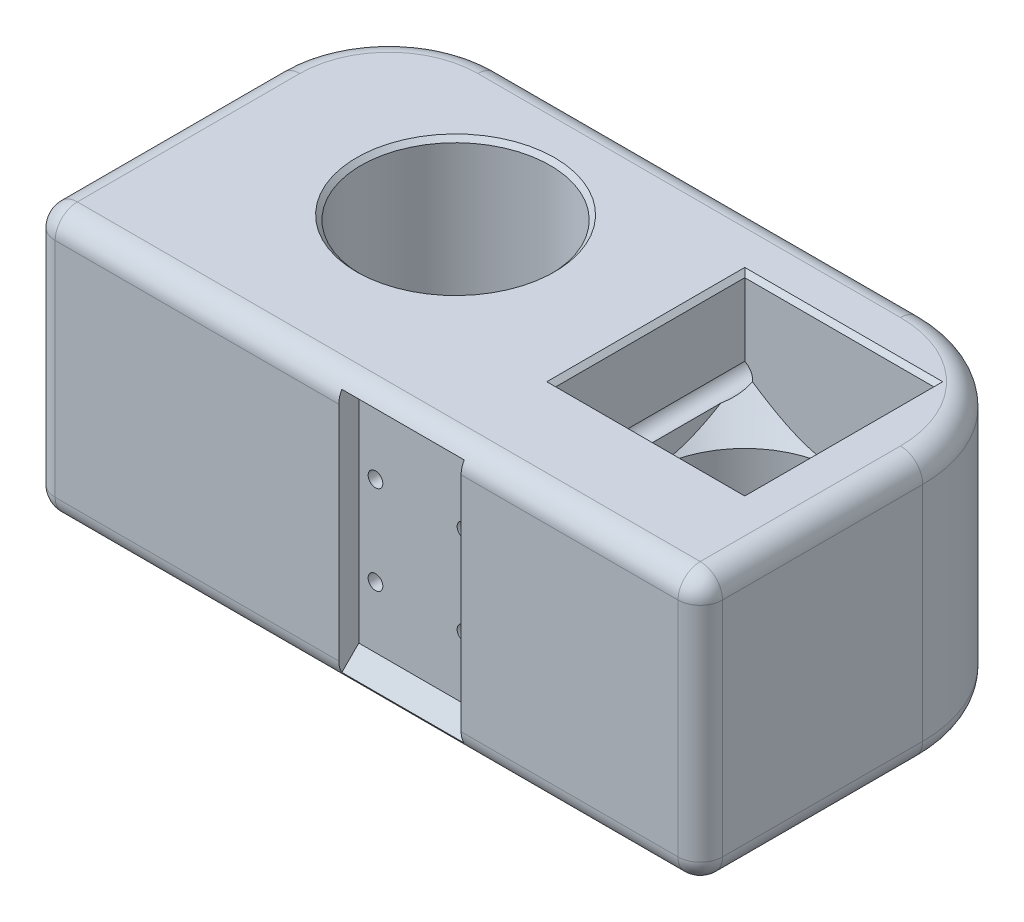
SolidWorks part; units mm, degrees
ref_plane "Front Plane" through (0, 0, 0) normal (0, 0, 1) x (1, 0, 0)
ref_plane "Top Plane" through (0, 0, 0) normal (0, 1, 0) x (1, 0, 0)
ref_plane "Right Plane" through (0, 0, 0) normal (1, 0, 0) x (0, 0, -1)
sketch "Sketch1" plane through (0, 0, 0) normal (0, 1, 0) x (1, 0, 0)
  line L1 (75, -40) -> (-75, -40)
  line L2 (75, -40) -> (75, 40)
  line L3 (75, 40) -> (-75, 40)
  line L4 (-75, -40) -> (-75, 40)
  line L5 (75, -40) -> (-75, 40) construction
  line L6 (75, 40) -> (-75, -40) construction
  point P0 (0, 0)
  dimension "D1" = 150
  dimension "D2" = 80
extrude "Boss-Extrude1" add sketch "Sketch1" along normal blind 60
sketch "Sketch2" plane through (0, 60, 0) normal (0, 1, 0) x (1, 0, 0)
  line L0 (-25, 5) -> (40, 5)
  line L1 (75, 40) -> (-75, 40) construction
  line L2 (75, -40) -> (75, 40) construction
  line L4 (18.75, -16.25) -> (61.25, -16.25)
  line L5 (18.75, -16.25) -> (18.75, 26.25)
  line L6 (18.75, 26.25) -> (61.25, 26.25)
  line L7 (61.25, -16.25) -> (61.25, 26.25)
  line L8 (18.75, -16.25) -> (61.25, 26.25) construction
  line L9 (18.75, 26.25) -> (61.25, -16.25) construction
  line L10 (-3.75, -16.25) -> (-46.25, -16.25)
  line L11 (-3.75, -16.25) -> (-3.75, 26.25)
  line L12 (-3.75, 26.25) -> (-46.25, 26.25)
  line L13 (-46.25, -16.25) -> (-46.25, 26.25)
  line L14 (-3.75, -16.25) -> (-46.25, 26.25) construction
  line L15 (-3.75, 26.25) -> (-46.25, -16.25) construction
  point P3 (7.5, 5)
  dimension "D1" = 65
  dimension "D2" = 35
  dimension "D3" = 35
  dimension "D4" = 42.5
  dimension "D5" = 42.5
  dimension "D6" = 42.5
  dimension "D7" = 42.5
extrude "Cut-Extrude1" cut sketch "Sketch2" against normal blind 60 contours L13 L10 L11 L12 | L4 L7 L6 L5 region at (19.351, 60, -15.625) region at (-4.351, 60, 5.625)
fillet "Fillet1" radius 30 1 edges at (75, 30, -40)
sketch "Sketch3" plane through (0, 0, 0) normal (0, -1, 0) x (1, 0, 0)
  line L0 (18.75, -26.25) -> (-3.75, -26.25)
  line L1 (7.5, -40) -> (7.5, 13.25)
  line L2 (45, -40) -> (-75, -40) construction
  line L3 (-6.465, 27.5) -> (-75, 27.5)
  line L4 (-3.75, 16.25) -> (-3.75, -26.25) construction
  line L6 (-75, -40) -> (-75, 40) construction
  line L7 (-75, 27.5) -> (-75, -40)
  line L8 (-75, -40) -> (7.5, -40)
  arc A0 (7.5, 13.25) -> (-6.465, 27.5) centre (-6.6075, 13.3925) ccw
  line M3 (-46.25, 16.25) -> (-3.75, 16.25)
  line M4 (-3.75, 16.25) -> (-3.75, -26.25)
  line M5 (-3.75, -26.25) -> (-46.25, -26.25)
  line M6 (-46.25, -26.25) -> (-46.25, 16.25)
  line M11 (-75, -40) -> (45, -40)
  line M15 (-75, 40) -> (-75, -40)
  dimension "D1" = 11.25
  dimension "D3" = 3
extrude "Cut-Extrude2" cut sketch "Sketch3" against normal blind 25 contours L1 A0 L3 M15 M11 M5 M6 M3 M4 region at (6.434, 0, -33.125)
fillet "Fillet2" radius 25 1 edges at (7.5, 12.5, -40)
fillet "Fillet3" radius 25 1 edges at (-75, 42.5, -40)
sketch "Sketch4" plane through (0, 0, 0) normal (0, -1, 0) x (1, 0, 0)
  line L0 (18.75, 16.25) -> (61.25, 16.25) construction
  line L1 (18.75, -26.25) -> (61.25, -26.25)
  line L2 (18.75, -26.25) -> (18.75, 16.25)
  line L3 (18.75, 16.25) -> (61.25, 16.25)
  line L4 (61.25, -26.25) -> (61.25, 16.25)
  line L5 (18.75, -26.25) -> (61.25, 16.25) construction
  line L6 (18.75, 16.25) -> (61.25, -26.25) construction
  circle A0 centre (40, -5) radius 11.75
  point P0 (40, -5)
  dimension "D1" = 23.5
extrude "Boss-Extrude2" add sketch "Sketch4" against normal blind 3
sketch "Sketch5" plane through (0, 3, 0) normal (0, 1, 0) x (1, 0, 0)
  line L1 (18.75, -16.25) -> (61.25, -16.25)
  line L2 (18.75, -16.25) -> (18.75, 26.25)
  line L3 (18.75, 26.25) -> (61.25, 26.25)
  line L4 (61.25, -16.25) -> (61.25, 26.25)
  line L5 (18.75, -16.25) -> (61.25, 26.25) construction
  line L6 (18.75, 26.25) -> (61.25, -16.25) construction
  circle A0 centre (40, 5) radius 21.25
  line M2 (61.25, -16.25) -> (61.25, 26.25)
  line M3 (61.25, 26.25) -> (18.75, 26.25)
  line M4 (18.75, 26.25) -> (18.75, -16.25)
  line M5 (18.75, -16.25) -> (61.25, -16.25)
  dimension "D1" = 42.5
extrude "Boss-Extrude3" add sketch "Sketch5" along normal blind 37 contours A0 L2 M5 | A0 L1 M2 | A0 L4 M3 | A0 L3 M4 region at (23.4966, 3, 11.5034) region at (56.5034, 3, 11.5034) region at (23.4966, 3, -21.5034) region at (56.5034, 3, -21.5034)
chamfer "Chamfer1" distance 8 angle 45 4 edges at (24.974, 40, -20.026) (55.026, 40, -20.026) (24.974, 40, 10.026) (55.026, 40, 10.026)
sketch "Sketch6" plane through (0, 25, 0) normal (0, -1, 0) x (1, 0, 0)
  line L1 (-3.75, -26.25) -> (-46.25, -26.25)
  line L2 (-3.75, -26.25) -> (-3.75, 16.25)
  line L3 (-3.75, 16.25) -> (-46.25, 16.25)
  line L4 (-46.25, -26.25) -> (-46.25, 16.25)
  line L5 (-3.75, -26.25) -> (-46.25, 16.25) construction
  line L6 (-3.75, 16.25) -> (-46.25, -26.25) construction
  circle A0 centre (-25, -5) radius 11.75
  point P0 (-25, -5)
  dimension "D1" = 23.5
extrude "Boss-Extrude4" add sketch "Sketch6" against normal blind 3
sketch "Sketch7" plane through (0, 28, 0) normal (0, 1, 0) x (1, 0, 0)
  line L1 (-46.25, -16.25) -> (-3.75, -16.25)
  line L2 (-46.25, -16.25) -> (-46.25, 26.25)
  line L3 (-46.25, 26.25) -> (-3.75, 26.25)
  line L4 (-3.75, -16.25) -> (-3.75, 26.25)
  line L5 (-46.25, -16.25) -> (-3.75, 26.25) construction
  line L6 (-46.25, 26.25) -> (-3.75, -16.25) construction
  circle A0 centre (-25, 5) radius 21.25
  line M2 (-46.25, 26.25) -> (-46.25, -16.25)
  line M3 (-46.25, -16.25) -> (-3.75, -16.25)
  line M4 (-3.75, -16.25) -> (-3.75, 26.25)
  line M5 (-3.75, 26.25) -> (-46.25, 26.25)
  dimension "D1" = 42.5
extrude "Boss-Extrude5" add sketch "Sketch7" along normal blind 32 contours A0 L1 M4 | A0 L2 M3 | A0 L3 M2 | A0 L4 M5 region at (-41.5034, 28, 11.5034) region at (-8.4966, 28, 11.5034) region at (-41.5034, 28, -21.5034) region at (-8.4966, 28, -21.5034)
fillet "Fillet4" radius 5 21 edges at (-75, 12.5, 27.5) (75, 60, 15) (66.2132, 60, -31.2132) (-2.5, 60, -40) (-75, 60, 12.5) (-75, 25, 6.25) (-67.6777, 25, -32.6777) (-40.7325, 25, 27.5) (3.4688, 25, 23.2672) (7.5, 25, -0.875) (3.4688, 0, 23.2672) (7.5, 0, -0.875) (75, 0, 15) (66.2132, 0, -31.2132) (38.75, 0, -40) (-67.6777, 60, -32.6777) (-75, 0, 33.75) (-8.75, 25, -40) (14.8223, 25, -32.6777) (-40.7325, 0, 27.5) (14.8223, 0, -32.6777)
sketch "Sketch9" plane through (0, 25, 0) normal (0, -1, 0) x (1, 0, 0)
  line L0 (-25, -5) -> (40, -5) construction
sketch "Sketch10" plane through (0, 0, 40) normal (0, 0, 1) x (1, 0, 0)
  line L0 (75, 55) -> (75, 5) construction
  line L1 (-6.25, 6.75) -> (21.25, 6.75)
  line L2 (-6.25, 6.75) -> (-6.25, 53.25)
  line L3 (-6.25, 53.25) -> (21.25, 53.25)
  line L4 (21.25, 6.75) -> (21.25, 53.25)
  line L5 (-6.25, 6.75) -> (21.25, 53.25) construction
  line L6 (-6.25, 53.25) -> (21.25, 6.75) construction
  point P0 (7.5, 30)
  point P7 (75, 30)
  dimension "D1" = 46.5
  dimension "D2" = 0
  dimension "D3" = 27.5
extrude "Cut-Extrude3" cut sketch "Sketch10" against normal blind 4.5
sketch "Sketch12" plane through (0, 0, 35.5) normal (0, 0, 1) x (1, 0, 0)
  line L7 (-25, 25) -> (40, 25) construction
  line L8 (75, 55) -> (75, 5) construction
  circle A0 centre (-2.5, 40) radius 1.65
  circle A1 centre (-2.5, 20) radius 1.65
  circle A2 centre (17.5, 20) radius 1.65
  circle A3 centre (17.5, 40) radius 1.65
  point P0 (7.5, 30)
  point P9 (7.5, 25)
  point P10 (75, 30)
  dimension "D5" = 3.3
  dimension "D6" = 3.3
  dimension "D1" = 20
  dimension "D2" = 20
  dimension "D3" = 0
  dimension "D4" = 0
extrude "Cut-Extrude4" cut sketch "Sketch12" against normal blind 94.5
sketch "Sketch13" plane through (0, 0, -40) normal (0, 0, -1) x (-1, 0, 0)
  circle A0 centre (-17.5, 40) radius 3
  circle A1 centre (2.5, 40) radius 3
  circle A2 centre (2.5, 20) radius 3
  circle A3 centre (-17.5, 20) radius 3
  dimension "D1" = 6
  dimension "D2" = 6
  dimension "D3" = 6
  dimension "D4" = 6
extrude "Cut-Extrude5" cut sketch "Sketch13" against normal blind 65
sketch "Sketch14" plane through (0, 0, 27.5) normal (0, 0, -1) x (-1, 0, 0)
  circle A0 centre (2.5, 20) radius 3
  circle A2 centre (2.5, 20) radius 1.65
  dimension "D1" = 6
extrude "Boss-Extrude6" add sketch "Sketch14" along normal up to surface (2.5 mm away) up to face at (-5.5, 40, 25)
fillet "Fillet5" radius 5 8 edges at (73.5355, 58.5355, 40) (0, 60, 40) (-73.5355, 58.5355, 40) (-75, 30, 40) (-73.5355, 1.4645, 40) (0, 0, 40) (73.5355, 1.4645, 40) (75, 30, 40)
chamfer "Chamfer2" distance 5 angle 45 2 edges at (7.5, 53.25, 40) (7.5, 6.75, 40)
chamfer "Chamfer3" distance 1 angle 45 5 edges at (40, 60, 16.25) (61.25, 60, -5) (40, 60, -26.25) (18.75, 60, -5) (-25, 60, 16.25)
